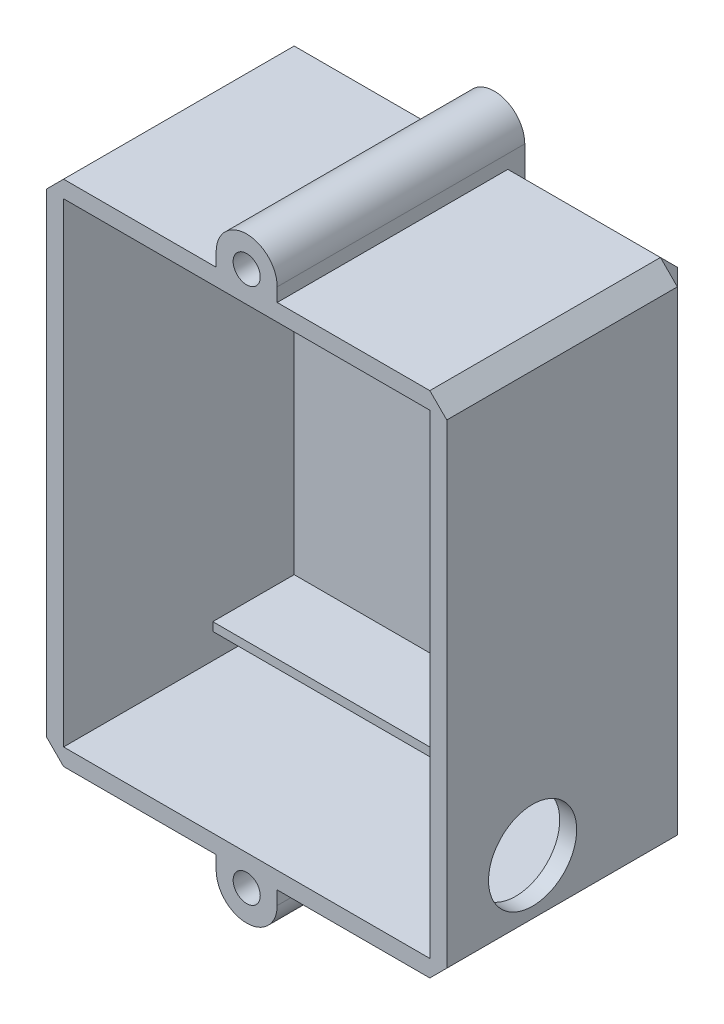
SolidWorks part; units mm, degrees
ref_plane "Front Plane" through (0, 0, 0) normal (0, 0, 1) x (1, 0, 0)
ref_plane "Top Plane" through (0, 0, 0) normal (0, 1, 0) x (1, 0, 0)
ref_plane "Right Plane" through (0, 0, 0) normal (1, 0, 0) x (0, 0, -1)
sketch "Sketch1" plane through (0, 0, 0) normal (0, 0, 1) x (1, 0, 0)
  line L0 (43.815, 9.525) -> (43.815, 75.5015)
  line L1 (0, 0) -> (31.75, 0)
  line L2 (0, 0) -> (0, 95.25)
  line L3 (0, 95.25) -> (31.75, 95.25)
  line L4 (74.93, 0) -> (74.93, 95.25)
  line L5 (3.175, 3.175) -> (71.755, 3.175)
  line L6 (3.175, 3.175) -> (3.175, 92.075)
  line L7 (3.175, 92.075) -> (71.755, 92.075)
  line L8 (71.755, 3.175) -> (71.755, 92.075)
  line L9 (43.815, 3.175) -> (45.4025, 3.175)
  line L10 (43.815, 3.175) -> (43.815, 7.9375)
  line L11 (43.815, 77.089) -> (45.4025, 77.089)
  line L12 (45.4025, 3.175) -> (45.4025, 77.089)
  line L13 (43.815, 77.089) -> (29.845, 77.089)
  line L15 (43.815, 75.5015) -> (29.845, 75.5015)
  line L16 (29.845, 77.089) -> (29.845, 75.5015)
  line L17 (3.175, 77.089) -> (17.145, 77.089)
  line L18 (3.175, 77.089) -> (3.175, 75.5015)
  line L19 (3.175, 75.5015) -> (17.145, 75.5015)
  line L20 (17.145, 77.089) -> (17.145, 75.5015)
  line L21 (3.175, 7.9375) -> (43.815, 7.9375)
  line L22 (3.175, 7.9375) -> (3.175, 9.525)
  line L23 (3.175, 9.525) -> (43.815, 9.525)
  line L25 (31.75, 97.79) -> (31.75, 95.25)
  line L26 (43.18, 97.79) -> (43.18, 95.25)
  line L27 (31.75, -2.54) -> (31.75, 0)
  line L28 (43.18, -2.54) -> (43.18, 0)
  line L29 (43.18, 0) -> (74.93, 0)
  line L31 (43.18, 95.25) -> (74.93, 95.25)
  circle A0 centre (37.465, -2.54) radius 2.54
  circle A1 centre (37.465, 97.79) radius 2.54
  arc A3 (31.75, -2.54) -> (43.18, -2.54) centre (37.465, -2.54) ccw
  arc A4 (43.18, 97.79) -> (31.75, 97.79) centre (37.465, 97.79) ccw
  dimension "D14" = 5.08
  dimension "D15" = 5.08
  dimension "D1" = 3.175
  dimension "D2" = 3.175
  dimension "D3" = 3.175
  dimension "D4" = 3.175
  dimension "D5" = 68.58
  dimension "D6" = 88.9
  dimension "D7" = 1.5875
  dimension "D8" = 40.64
  dimension "D9" = 73.914
  dimension "D10" = 1.5875
  dimension ".0625" = 1.5875
  dimension "D11" = 12.7
  dimension "D12" = 1.5875
  dimension "D13" = 6.35
  dimension "D16" = 34.29
  dimension "D17" = 34.29
  dimension "D18" = 2.54
  dimension "D19" = 2.54
extrude "Boss-Extrude1" add sketch "Sketch1" against normal blind 3.175 contours L2 L3 L25 A4 L26 L31 L4 L29 L28 A3 L27 L1 | A1 | A0
extrude "Boss-Extrude2" add sketch "Sketch1<3>" along normal blind 10.16 contours L19 L20 L17 L18 | L15 L16 L13 L11 L12 L9 L10 L21 L22 L23 L0
sketch "Sketch1<3>" plane through (0, 0, 0) normal (0, 0, 1) x (1, 0, 0) same geometry as "Sketch1"
extrude "Boss-Extrude3" add sketch "Sketch1<4>" along normal blind 43.18 contours L1 L4 L3 L2 L8 L5 L6 L7 region at (1.3455, 47.625, 0)
sketch "Sketch1<4>" plane through (0, 0, 0) normal (0, 0, 1) x (1, 0, 0) same geometry as "Sketch1"
sketch "Sketch2" plane through (0, 0, 0) normal (0, 0, 1) x (1, 0, 0)
  line L0 (3.175, 77.089) -> (3.175, 92.075) construction
  line L1 (3.175, 82.9945) -> (17.145, 82.9945)
  line L2 (3.175, 82.9945) -> (3.175, 81.407)
  line L3 (3.175, 81.407) -> (17.145, 81.407)
  line L5 (3.175, 3.175) -> (43.815, 3.175) construction
  line L6 (45.4025, 3.175) -> (71.755, 3.175) construction
  line L7 (54.737, 82.9945) -> (55.74, 82.9945)
  line L8 (54.1525, 81.407) -> (54.1525, 52.6097)
  line L9 (54.1525, 3.175) -> (55.74, 3.175)
  line L10 (55.74, 82.9945) -> (55.74, 52.6097)
  line L11 (17.145, 82.9945) -> (17.145, 81.407)
  line L12 (29.845, 82.9945) -> (29.845, 81.407)
  line L13 (17.145, 77.089) -> (17.145, 75.5015) construction
  line L14 (29.845, 77.089) -> (29.845, 75.5015) construction
  line L15 (29.845, 81.407) -> (54.1525, 81.407)
  line L16 (29.845, 82.9945) -> (54.737, 82.9945)
  line L17 (54.1525, 52.6097) -> (55.74, 52.6097)
  line L18 (54.1525, 33.5598) -> (55.74, 33.5598)
  line L19 (54.1525, 33.5598) -> (54.1525, 9.525)
  line L20 (55.74, 33.5598) -> (55.74, 3.175)
  line L21 (54.1525, 7.9375) -> (54.1525, 3.175)
  line L22 (3.175, 9.525) -> (54.1525, 9.525)
  line L23 (3.175, 9.525) -> (3.175, 7.9375)
  line L24 (3.175, 7.9375) -> (54.1525, 7.9375)
  dimension "D1" = 1.5875
  dimension "D2" = 51.562
  dimension "D3" = 78.232
  dimension "D4" = 1.5875
  dimension "D5" = 19.05
  dimension "D6" = 1.5875
extrude "Boss-Extrude4" add sketch "Sketch2" along normal blind 15.24
sketch "Sketch3" plane through (71.755, 0, 0) normal (-1, 0, 0) x (0, 0, 1)
  line L0 (43.18, 3.175) -> (0, 3.175) construction
  line L1 (0, 3.175) -> (0, 92.075) construction
  circle A0 centre (27.1145, 13.462) radius 8.255
  dimension "D3" = 16.51
  dimension "D1" = 10.287
  dimension "D2" = 27.1145
extrude "Cut-Extrude1" cut sketch "Sketch3" against normal blind 15.24
chamfer "Chamfer1" distance 3.175 angle 45 10 edges at (74.93, 0, 20.0025) (74.93, 95.25, 20.0025) (59.055, 95.25, -3.175) (74.93, 47.625, -3.175) (59.055, 0, -3.175) (0, 0, 20.0025) (0, 95.25, 20.0025) (15.875, 95.25, -3.175) (15.875, 0, -3.175) (0, 47.625, -3.175)
